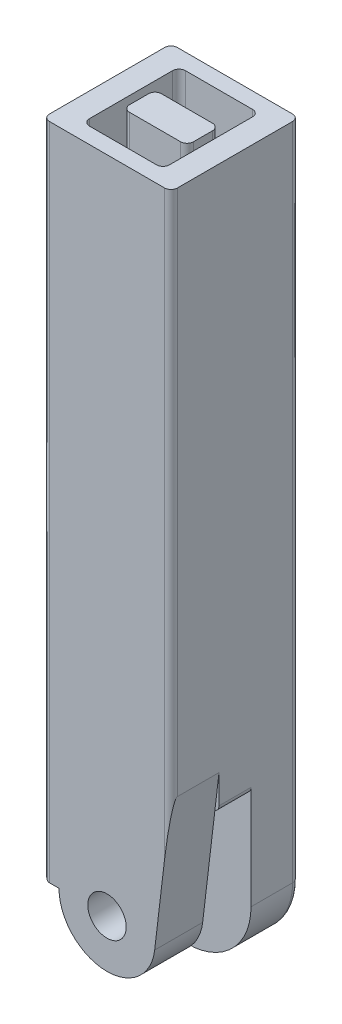
SolidWorks part; units mm, degrees
material "Ti-6Al-4VSolution treated and aged (SS)"
ref_plane "Front Plane" through (0, 0, 0) normal (0, 0, 1) x (1, 0, 0)
ref_plane "Top Plane" through (0, 0, 0) normal (0, 1, 0) x (1, 0, 0)
ref_plane "Right Plane" through (0, 0, 0) normal (1, 0, 0) x (0, 0, -1)
sketch "Sketch1" plane through (0, 0, 0) normal (0, 0, 1) x (1, 0, 0)
  line L4 (0, -10) -> (0, -5)
  line L6 (-7.5, 0) -> (-7.0711, 0)
  line L7 (-10, 2.5) -> (-10, 103)
  line L8 (-10, 103) -> (10, 103)
  line L9 (10, 0) -> (10, 103)
  arc A4 (0, -10) -> (10, 0) centre (0, 0) ccw
  arc A5 (-4.714, -1.6667) -> (0, -5) centre (0, 0) ccw
  arc A6 (-4.714, -1.6667) -> (-7.0711, 0) centre (-7.0711, -2.5) ccw
  arc A7 (-7.5, 0) -> (-10, 2.5) centre (-7.5, 2.5) cw
  point P6 (0, 51.5)
  point P13 (-10, 0)
  dimension "D1" = 20
  dimension "D2" = 5
  dimension "D4" = 103
  dimension "D3" = 20
  dimension "D5" = 2.5
extrude "Boss-Extrude1" add sketch "Sketch1" along normal blind 7.5
sketch "Sketch2" plane through (0, 0, 7.5) normal (0, 0, 1) x (1, 0, 0)
  line L5 (-10, 103) -> (10, 103)
  line L7 (-10, 103) -> (-10, 14.3614)
  line L9 (10, 103) -> (10, 14.3614)
  arc A6 (10, 14.3614) -> (-10, 14.3614) centre (0, 0) ccw
  point P2 (0, 51.5)
  point P16 (-10, 0)
  dimension "D1" = 35
  dimension "D3" = 103
  dimension "D4" = 20
extrude "Boss-Extrude2" add sketch "Sketch2" along normal blind 5
sketch "Sketch3" plane through (0, 0, 12.5) normal (0, 0, 1) x (1, 0, 0)
  line L24 (7.4479, -0.8824) -> (10, 20.6597)
  line L37 (-7.5, 0) -> (-10, 0)
  line L38 (10, 103) -> (-10, 103)
  line L39 (10, 103) -> (10, 20.6597)
  line L41 (-10, 103) -> (-10, 0)
  arc A19 (-7.5, 0) -> (7.4479, -0.8824) centre (0, 0) ccw
extrude "Boss-Extrude3" add sketch "Sketch3" along normal blind 7.5
sketch "Sketch4" plane through (0, 0, 0) normal (0, 0, -1) x (-1, 0, 0)
  circle A0 centre (0, 0) radius 3
  dimension "D1" = 6
extrude "Cut-Extrude1" cut sketch "Sketch4" against normal through all
sketch "Sketch5" plane through (0, 103, 0) normal (0, 1, 0) x (1, 0, 0)
  line L13 (10, 0) -> (-10, 0) construction
  line L14 (-4, -12.5) -> (4, -12.5)
  line L15 (-5, -11.5) -> (-5, -8.5)
  line L16 (-4, -7.5) -> (4, -7.5)
  line L17 (5, -11.5) -> (5, -8.5)
  line L18 (-5, -12.5) -> (5, -7.5) construction
  line L19 (-5, -7.5) -> (5, -12.5) construction
  line L21 (-5.25, -17.5) -> (5.25, -17.5)
  line L22 (-6.25, -16.5) -> (-6.25, -3.5)
  line L23 (-5.25, -2.5) -> (5.25, -2.5)
  line L24 (6.25, -16.5) -> (6.25, -3.5)
  line L25 (-6.25, -17.5) -> (6.25, -2.5) construction
  line L26 (-6.25, -2.5) -> (6.25, -17.5) construction
  arc A8 (5.25, -17.5) -> (6.25, -16.5) centre (5.25, -16.5) ccw
  arc A9 (-5.25, -17.5) -> (-6.25, -16.5) centre (-5.25, -16.5) cw
  arc A10 (-6.25, -3.5) -> (-5.25, -2.5) centre (-5.25, -3.5) cw
  arc A11 (5.25, -2.5) -> (6.25, -3.5) centre (5.25, -3.5) cw
  arc A12 (4, -7.5) -> (5, -8.5) centre (4, -8.5) cw
  arc A13 (4, -12.5) -> (5, -11.5) centre (4, -11.5) ccw
  arc A14 (-4, -12.5) -> (-5, -11.5) centre (-4, -11.5) cw
  arc A15 (-5, -8.5) -> (-4, -7.5) centre (-4, -8.5) cw
  point P0 (0, -10)
  point P8 (0, -10)
  dimension "D2" = 5
  dimension "D6" = 1
  dimension "D1" = 10
  dimension "D3" = 10
  dimension "D4" = 12.5
  dimension "D5" = 15
extrude "Cut-Extrude2" cut sketch "Sketch5" against normal blind 14.1
fillet "Fillet1" radius 1 12 edges at (-10, 52.75, 0) (-9.2678, 0.7322, 0) (-2.8868, -4.0825, 0) (-5.6277, -0.4588, 0) (-7.2855, 0, 0) (7.0711, -7.0711, 0) (-10, 51.5, 20) (-10, 0, 16.25) (10, 14.3614, 10) (10, 61.8299, 20) (10, 51.5, 0) (0, -10, 3.75)
hole_wizard "M3x0.5 Tapped Hole1" positions "Sketch10" profile "Sketch11" tap size "M3x0.5" standard "ANSI Metric"
sketch "Sketch10" plane through (-10, 0, 0) normal (-1, 0, 0) x (0, 0, 1)
  line L0 (19, 103) -> (1, 103) construction
  line L1 (20, 103) -> (20, 0) construction
  line L2 (0, 2.5) -> (0, 103) construction
  point P0 (15, 95.95)
  point P7 (5, 95.95)
  dimension "D1" = 7.05
  dimension "D2" = 5
  dimension "D3" = 5
cosmetic thread "Hole Thread4" parameters "D1"=18, "D2"=3
sketch "Sketch11" plane through (-10, 95.95, 15) normal (0, 1, 0) x (0, 0, 1)
  line L0 (0, 0) -> (0, 18.7511)
  line L1 (0, 18.7511) -> (1.25, 18)
  line L2 (1.25, 18) -> (1.25, 1.55)
  line L3 (1.25, 1.55) -> (2.8, 0)
  line L5 (2.8, 0) -> (0, 0)
  line L6 (-1.25, 1.55) -> (-2.8, 0) construction
  line L10 (0, 18.7511) -> (-1.25, 18) construction
  line L11 (0, -6.35) -> (0, 107.95) construction
  dimension "Tap Drill Dia." = 2.5
  dimension "Tap Drill Depth" = 18
  dimension "Near C'Sink Dia." = 5.6
  dimension "Near C'Sink Angle" = 90
  dimension "Drill Angle" = 118
cosmetic thread "Hole Thread5" parameters "D1"=18, "D2"=3
equation "\"D1@Boss-Extrude3\" =  ( \"t_thigh\" - 0.005m )  / 2"
equation "\"D1@Boss-Extrude2\"=\"t_lowerThighCutout\""
equation "\"D1@Boss-Extrude1\" =  ( \"t_thigh\" - 0.005m )  / 2"
equation "\"t_thigh\"= 0.0200m"
equation "\"D2@Sketch10\" = \"t_thigh\" / 4"
equation "\"D3@Sketch5\" = \"t_thigh\" / 2"
equation "\"D5@Sketch5\" = \"t_thigh\" - 0.005m"
equation "\"D3@Sketch10\" = \"t_thigh\" / 4"
equation "\"L_upperThigh\"= 0.2952m"
